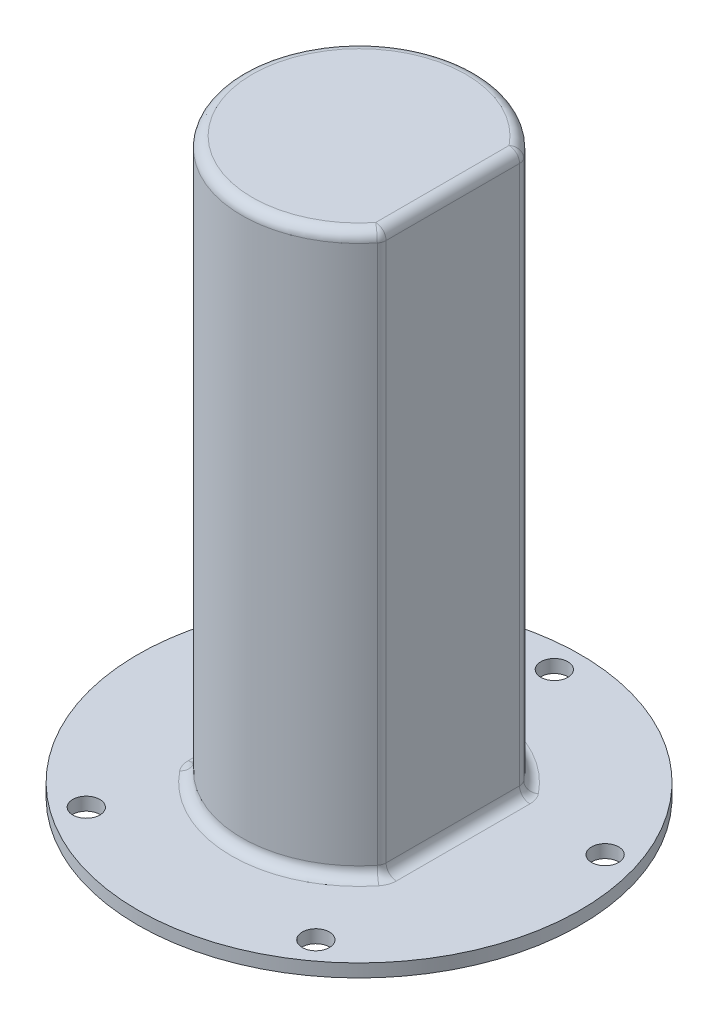
SolidWorks part; units mm, degrees
material "6061-T6 (SS)"
ref_plane "Front Plane" through (0, 0, 0) normal (0, 0, 1) x (1, 0, 0)
ref_plane "Top Plane" through (0, 0, 0) normal (0, 1, 0) x (1, 0, 0)
ref_plane "Right Plane" through (0, 0, 0) normal (1, 0, 0) x (0, 0, -1)
sketch "Sketch1" plane through (0, 0, 0) normal (0, 1, 0) x (1, 0, 0)
  line L0 (0, 0) -> (0, 47.625) construction
  line L1 (0, 0) -> (45.2941, 14.7169) construction
  circle A0 centre (0, 0) radius 53.975
  circle A1 centre (0, 47.625) radius 3.302
  circle A2 centre (45.2941, 14.7169) radius 3.302
  circle A3 centre (27.9933, -38.5294) radius 3.302
  circle A4 centre (-27.9933, -38.5294) radius 3.302
  circle A5 centre (-45.2941, 14.7169) radius 3.302
  dimension "D1" = 107.95
  dimension "D2" = 6.604
  dimension "D3" = 47.625
  dimension "D5" = 72
  dimension "D6" = 47.625
  dimension "D4" = 5
extrude "Boss-Extrude1" add sketch "Sketch1" along normal blind 3.175
sketch "Sketch2" plane through (0, 3.175, 0) normal (0, 1, 0) x (1, 0, 0)
  circle A0 centre (0, 0) radius 28.575
  dimension "D1" = 57.15
extrude "Boss-Extrude2" add sketch "Sketch2" along normal blind 136.525
sketch "Sketch3" plane through (0, 139.7, 0) normal (0, 1, 0) x (1, 0, 0)
  line L1 (22.86, 17.145) -> (63.311, 17.145)
  line L2 (22.86, 17.145) -> (22.86, -17.145)
  line L3 (22.86, -17.145) -> (63.311, -17.145)
  line L4 (63.311, 17.145) -> (63.311, -17.145)
  circle A0 centre (0, 0) radius 28.575 construction
  circle A1 centre (0, 0) radius 28.575 construction
  dimension "D1" = 22.86
extrude "Cut-Extrude1" cut sketch "Sketch3" against normal up to surface (136.525 mm away) up to face at (-45.2941, 3.175, -11.4149)
sketch "Sketch4" plane through (0, 3.175, 0) normal (0, 1, 0) x (1, 0, 0)
  line L1 (-22.86, -17.145) -> (-47.5319, -17.145)
  line L2 (-22.86, -17.145) -> (-22.86, 17.145)
  line L3 (-22.86, 17.145) -> (-47.5319, 17.145)
  line L4 (-47.5319, -17.145) -> (-47.5319, 17.145)
  arc A0 (22.86, 17.145) -> (22.86, -17.145) centre (0, 0) ccw construction
  circle A1 centre (-45.2941, 14.7169) radius 3.302 construction
  dimension "D1" = 22.86
extrude "Cut-Extrude2" cut sketch "Sketch4" along normal blind 49.53
fillet "Fillet1" radius 2.54 11 edges at (0, 3.175, 28.575) (0, 3.175, -28.575) (22.86, 71.4375, 17.145) (22.86, 71.4375, -17.145) (22.86, 3.175, 0) (-22.86, 27.94, 17.145) (-22.86, 27.94, -17.145) (-28.575, 52.705, 0) (-22.86, 3.175, 0) (22.86, 139.7, 0) (-28.575, 139.7, 0)
